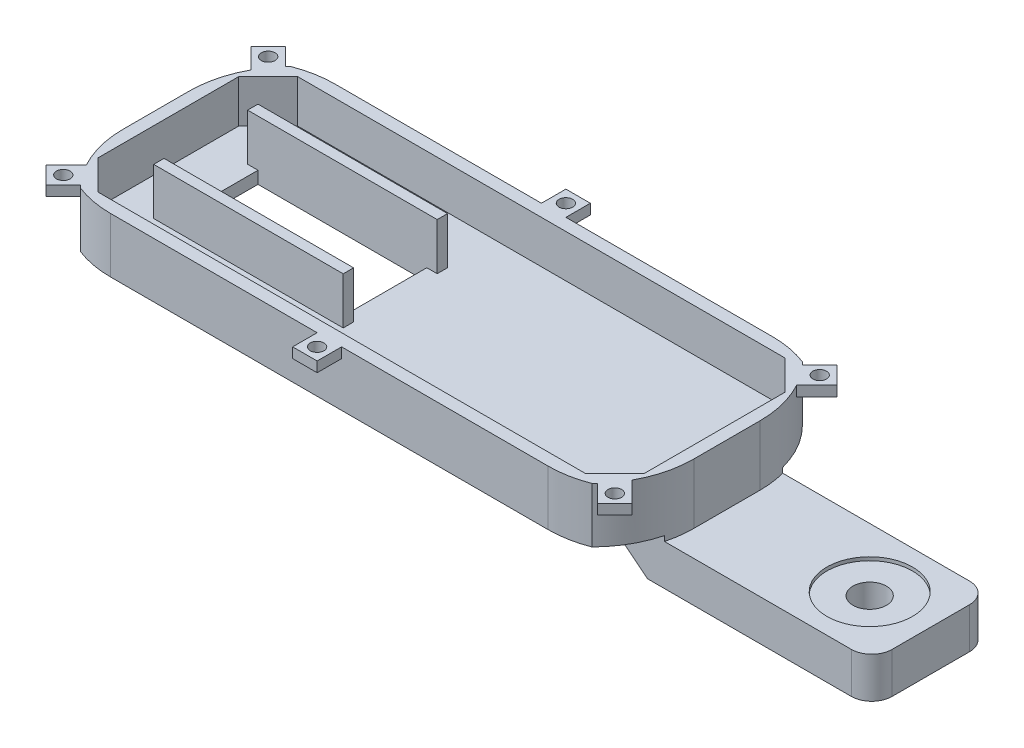
SolidWorks part; units mm, degrees
ref_plane "Front Plane" through (0, 0, 0) normal (0, 0, 1) x (1, 0, 0)
ref_plane "Top Plane" through (0, 0, 0) normal (0, 1, 0) x (1, 0, 0)
ref_plane "Right Plane" through (0, 0, 0) normal (1, 0, 0) x (0, 0, -1)
sketch "Sketch1" plane through (0, 0, 0) normal (0, 1, 0) x (1, 0, 0)
  line L0 (0, 46) -> (9, 55)
  line L1 (9, 0) -> (131, 0)
  line L2 (0, 9) -> (0, 46)
  line L3 (9, 55) -> (131, 55)
  line L4 (140, 9) -> (140, 46)
  line L5 (0, 9) -> (9, 0)
  line L6 (131, 55) -> (140, 46)
  line L7 (131, 0) -> (140, 9)
  point P0 (0, 0)
  point P1 (140, 55)
  point P2 (0, 55)
  point P3 (140, 0)
  dimension "D1" = 55
  dimension "D2" = 140
extrude "Boss-Extrude1" add sketch "Sketch1" along normal blind 30
sketch "Sketch2" plane through (0, 30, 0) normal (0, 1, 0) x (1, 0, 0)
  line L8 (3, 44.7574) -> (3, 10.2426)
  line L9 (10.2426, 3) -> (129.7574, 3)
  line L10 (137, 10.2426) -> (137, 44.7574)
  line L11 (129.7574, 52) -> (10.2426, 52)
  line L12 (3, 44.7574) -> (3, 10.2426)
  line L13 (10.2426, 3) -> (129.7574, 3)
  line L14 (137, 10.2426) -> (137, 44.7574)
  line L15 (129.7574, 52) -> (10.2426, 52)
  line L20 (3, 10.2426) -> (10.2426, 3)
  line L21 (3, 10.2426) -> (10.2426, 3)
  line L22 (129.7574, 3) -> (137, 10.2426)
  line L23 (129.7574, 3) -> (137, 10.2426)
  line L24 (137, 44.7574) -> (129.7574, 52)
  line L25 (137, 44.7574) -> (129.7574, 52)
  line L26 (10.2426, 52) -> (3, 44.7574)
  line L27 (10.2426, 52) -> (3, 44.7574)
  dimension "D1" = 3
shell "Shell2" thickness 3
extrude "Cut-Extrude2" cut sketch "Sketch2" against normal up to next
sketch "Length from bottom to Gear/Pin connection" plane through (0, 0, 0) normal (0, -1, 0) x (1, 0, 0)
  line L0 (0, -27.5) -> (25, -27.5) construction
  line L1 (0, -13.6125) -> (0, 13.6125) construction
  circle A0 centre (25, -27.5) radius 6.9102
  dimension "D1" = 25
sketch "Sketch4" plane through (0, 0, 0) normal (0, -1, 0) x (1, 0, 0)
  circle A0 centre (25, -27.5) radius 3.8
  dimension "D1" = 7.6
sketch "Outline of actual motor" plane through (0, 3, 0) normal (0, 1, 0) x (1, 0, 0)
  line L0 (15, 37.5) -> (55.9, 37.5) construction
  line L1 (55.9, 37.5) -> (55.9, 17.5) construction
  line L2 (55.9, 17.5) -> (15, 17.5) construction
  line L3 (15, 17.5) -> (15, 37.5) construction
  line L4 (55.2, 37.5) -> (15.7, 37.5) construction
  line L5 (15.7, 17.5) -> (55.2, 17.5) construction
  line L6 (55.9, 18.2) -> (55.9, 36.8) construction
  line L7 (15, 36.8) -> (15, 18.2) construction
  dimension "D1" = 0
  dimension "D2" = 0
  dimension "D3" = 0
  dimension "D4" = 0
sketch "Outline of motor press fit" plane through (0, 3, 0) normal (0, 1, 0) x (1, 0, 0)
  line L8 (15, 37.5) -> (55.9, 37.5) construction
  line L9 (14.75, 17.25) -> (56.15, 17.25)
  line L10 (14.75, 17.25) -> (14.75, 37.75)
  line L11 (14.75, 37.75) -> (56.15, 37.75)
  line L12 (56.15, 17.25) -> (56.15, 37.75)
  line L13 (55.9, 37.5) -> (55.9, 17.5) construction
  line L14 (55.9, 17.5) -> (15, 17.5) construction
  line L15 (15, 17.5) -> (15, 37.5) construction
  dimension "D1" = 0.25
  dimension "D2" = 0.25
  dimension "D3" = 0.25
  dimension "D4" = 0.25
sketch "Sketch16" plane through (0, 3, 0) normal (0, 1, 0) x (1, 0, 0)
  line L0 (18.21, 40.29) -> (52.69, 40.29)
  line L1 (52.69, 37.75) -> (18.21, 37.75)
  line L2 (18.21, 17.25) -> (52.69, 17.25)
  line L3 (52.69, 14.71) -> (18.21, 14.71)
  line L4 (14.75, 37.75) -> (12.21, 37.75)
  line L5 (12.21, 37.75) -> (58.69, 37.75)
  line L6 (58.69, 17.25) -> (56.15, 17.25)
  line L7 (12.21, 17.25) -> (14.75, 17.25)
  line L8 (12.21, 40.29) -> (18.21, 40.29) construction
  line L9 (12.21, 40.29) -> (12.21, 37.75) construction
  line L12 (12.21, 14.71) -> (58.69, 14.71)
  line L13 (58.69, 14.71) -> (58.69, 40.29)
  line L14 (58.69, 40.29) -> (12.21, 40.29)
  line L15 (12.21, 40.29) -> (12.21, 14.71)
  line L16 (12.21, 14.71) -> (18.21, 14.71)
  line L17 (58.69, 14.71) -> (58.69, 17.25)
  line L18 (58.69, 40.29) -> (52.69, 40.29)
  line L19 (12.21, 40.29) -> (12.21, 37.75)
  line L21 (14.75, 37.75) -> (56.15, 37.75) construction
  line L22 (18.21, 37.75) -> (14.75, 37.75)
  line L24 (35.45, 40.29) -> (35.45, 14.71) construction
  line L25 (12.21, 27.5) -> (58.69, 27.5) construction
  line L26 (18.21, 40.29) -> (12.21, 40.29)
  line L27 (12.21, 17.25) -> (12.21, 14.71)
  line L29 (58.69, 40.29) -> (58.69, 37.75)
  line L31 (52.69, 37.75) -> (56.15, 37.75)
  line L33 (52.69, 40.29) -> (58.69, 40.29)
  line L34 (52.69, 14.71) -> (58.69, 14.71)
  line L36 (52.69, 17.25) -> (56.15, 17.25)
  line L39 (58.69, 14.71) -> (58.69, 17.25)
  line L40 (18.21, 14.71) -> (12.21, 14.71)
  line L42 (18.21, 17.25) -> (14.75, 17.25)
  line L45 (12.21, 14.71) -> (12.21, 17.25)
  line L46 (58.69, 37.75) -> (58.69, 40.29)
  line L47 (52.69, 14.71) -> (58.69, 14.71)
  dimension "D2" = 6
  dimension "D1" = 2.54
extrude "Boss-Extrude5" add sketch "Sketch16" along normal blind 25.5 contours L29 L18 L0 L26 L19 L4 L5 L1 | L2 L42 L7 L27 L16 L3 L34 L17 L6 L36 region at (35.45, 3, -39.02) region at (35.45, 3, -15.98)
sketch "Sketch17" plane through (0, 28.5, 0) normal (0, 1, 0) x (1, 0, 0)
  line L0 (58.69, 40.29) -> (12.21, 40.29) construction
  line L1 (56.193, 40.29) -> (64.193, 40.29)
  line L2 (56.193, 40.29) -> (56.193, 14.71)
  line L3 (56.193, 14.71) -> (64.193, 14.71)
  line L4 (64.193, 40.29) -> (64.193, 14.71)
  line L5 (14.75, 37.75) -> (14.75, 40.29) construction
  line L6 (58.69, 40.29) -> (12.21, 40.29) construction
  line L8 (14.75, 40.29) -> (6.75, 40.29)
  line L9 (14.75, 40.29) -> (14.75, 14.71)
  line L10 (14.75, 14.71) -> (6.75, 14.71)
  line L11 (6.75, 40.29) -> (6.75, 14.71)
  dimension "D1" = 8
  dimension "D2" = 8
extrude "Boss-Extrude6" add sketch "Sketch17" against normal blind 5
sketch "Sketch18" plane through (0, 28.5, 0) normal (0, 1, 0) x (1, 0, 0)
  circle A0 centre (59.75, 32.5) radius 1.75
  circle A1 centre (59.75, 22.5) radius 1.75
  circle A2 centre (11.15, 22.5) radius 1.75
  circle A3 centre (11.15, 32.5) radius 1.75
  dimension "D1" = 3.5
  dimension "D2" = 3.5
  dimension "D3" = 3.5
  dimension "D4" = 3.5
extrude "Cut-Extrude3" cut sketch "Sketch18" against normal up to next
sketch "Sketch20" plane through (0, 30, 0) normal (0, 1, 0) x (1, 0, 0)
  line L1 (-8.4121, 65.847) -> (189.0699, 65.847)
  line L2 (-8.4121, 65.847) -> (-8.4121, -17.3253)
  line L3 (-8.4121, -17.3253) -> (189.0699, -17.3253)
  line L4 (189.0699, 65.847) -> (189.0699, -17.3253)
extrude "Cut-Extrude4" cut sketch "Sketch20" against normal offset from surface (16.5 mm away) 13.5 up to face at (70, 0, -27.5)
sketch "Sketch21" plane through (0, 0, 0) normal (0, 0, 1) x (1, 0, 0)
  line L0 (80.8737, 0) -> (80.8737, 13.5) construction
  line L1 (30.25, 0) -> (-30.25, 0) construction
  dimension "D1" = 13.5
extrude "Cut-Extrude5" cut sketch "Outline of motor press fit" against normal up to next
sketch "Sketch24" plane through (0, 13.5, 0) normal (0, 1, 0) x (1, 0, 0)
  line L1 (12.21, 40.29) -> (58.69, 40.29)
  line L2 (12.21, 40.29) -> (12.21, 37.75)
  line L3 (12.21, 37.75) -> (58.69, 37.75)
  line L4 (58.69, 40.29) -> (58.69, 37.75)
  line L5 (12.21, 17.25) -> (58.69, 17.25)
  line L6 (12.21, 17.25) -> (12.21, 14.71)
  line L7 (12.21, 14.71) -> (58.69, 14.71)
  line L8 (58.69, 17.25) -> (58.69, 14.71)
extrude "Boss-Extrude7" add sketch "Sketch24" along normal blind 1
sketch "Sketch25" plane through (140, 0, 0) normal (1, 0, 0) x (0, 0, -1)
  line L0 (27.5, 0) -> (27.5, -1.25) construction
  line L1 (20.5898, 0) -> (34.4102, 0) construction
  line L2 (27.5, 0) -> (27.5, -11.25) construction
  dimension "D1" = 1.25
  dimension "D2" = 11.25
sketch "Sketch26" plane through (140, 0, 0) normal (1, 0, 0) x (0, 0, -1)
  line L0 (27.5, 0) -> (42, 0) construction
  line L1 (20.5898, 0) -> (34.4102, 0) construction
  line L2 (9, 0) -> (46, 0) construction
  line L3 (27.5, 0) -> (13, 0) construction
  line L5 (13, 0) -> (42, 0)
  line L6 (13, 0) -> (13, -11.25)
  line L7 (13, -11.25) -> (42, -11.25)
  line L8 (42, 0) -> (42, -11.25)
  dimension "D1" = 14.5
  dimension "D2" = 14.5
extrude "Boss-Extrude8" add sketch "Sketch26" along normal blind 55 from offset 5 offset against normal yes
sketch "Sketch27" plane through (0, 0, -13) normal (0, 0, 1) x (1, 0, 0)
  line L0 (135, -11.25) -> (121, 0)
  line L1 (9, 0) -> (131, 0) construction
  line L2 (121, 0) -> (135, 0)
  line L3 (135, 0) -> (135, -11.25) construction
  line L4 (131, 0) -> (140, 0) construction
  line L5 (135, 0) -> (135, -11.25)
  dimension "D1" = 14
extrude "Boss-Extrude9" add sketch "Sketch27" against normal up to surface (29 mm away) up to face at (158, -4.5, -42)
sketch "Sketch31" plane through (190, 0, 0) normal (1, 0, 0) x (0, 0, -1)
  line L0 (13, 0) -> (13, -11.25) construction
  line L1 (42, 0) -> (13, 0)
  line L2 (42, 0) -> (42, -1.25)
  line L3 (42, -1.25) -> (13, -1.25)
  line L4 (13, 0) -> (13, -1.25)
  dimension "D1" = 1.25
extrude "Cut-Extrude8" cut sketch "Sketch31" against normal up to surface (50 mm away) up to face at (140, 4.5, -27.5)
sketch "Sketch32" plane through (0, -1.25, 0) normal (0, 1, 0) x (1, 0, 0)
  line L0 (140, 27.5) -> (175, 27.5) construction
  line L1 (140, 46) -> (140, 9) construction
  circle A0 centre (175, 27.5) radius 10.5
  dimension "D2" = 21
  dimension "D1" = 35
extrude "Cut-Extrude9" cut sketch "Sketch32" against normal blind 0.85
sketch "Sketch33" plane through (0, -2.1, 0) normal (0, 1, 0) x (1, 0, 0)
  circle A0 centre (175, 27.5) radius 4.1
  dimension "D1" = 8.2
extrude "Cut-Extrude10" cut sketch "Sketch33" against normal blind 7.25
sketch "Sketch35" plane through (0, 13.5, 0) normal (0, 1, 0) x (1, 0, 0)
  line L0 (0, 27.5) -> (53, 27.5) construction
  line L1 (9, 55) -> (0, 46) construction
  line L2 (9, 55) -> (131, 55) construction
  line L3 (73, 55) -> (67, 55)
  line L4 (0, -14.1625) -> (0, 14.1625) construction
  line L5 (0, 46) -> (9, 55) construction
  line L6 (6.6213, 52.6213) -> (2.3787, 48.3787)
  line L7 (2.3787, 48.3787) -> (-1.864, 52.6213)
  line L8 (-1.864, 52.6213) -> (2.3787, 56.864)
  line L9 (2.3787, 56.864) -> (6.6213, 52.6213)
  line L10 (131, 55) -> (140, 46) construction
  line L11 (137.6213, 48.3787) -> (133.3787, 52.6213)
  line L12 (133.3787, 52.6213) -> (137.6213, 56.864)
  line L13 (137.6213, 56.864) -> (141.864, 52.6213)
  line L14 (141.864, 52.6213) -> (137.6213, 48.3787)
  line L15 (67, 55) -> (67, 61)
  line L16 (67, 61) -> (73, 61)
  line L17 (73, 61) -> (73, 55)
  line L18 (137.6213, -1.864) -> (141.864, 2.3787)
  line L19 (133.3787, 2.3787) -> (137.6213, -1.864)
  line L20 (137.6213, 6.6213) -> (133.3787, 2.3787)
  line L21 (141.864, 2.3787) -> (137.6213, 6.6213)
  line L22 (67, -6) -> (73, -6)
  line L23 (67, 0) -> (67, -6)
  line L24 (73, 0) -> (67, 0)
  line L25 (73, -6) -> (73, 0)
  line L26 (-1.864, 2.3787) -> (2.3787, -1.864)
  line L27 (2.3787, 6.6213) -> (-1.864, 2.3787)
  line L28 (6.6213, 2.3787) -> (2.3787, 6.6213)
  line L29 (2.3787, -1.864) -> (6.6213, 2.3787)
  point P13 (4.5, 50.5)
  point P22 (135.5, 50.5)
  point P27 (70, 55)
  dimension "D1" = 6
  dimension "D2" = 6
  dimension "D3" = 6
  dimension "D4" = 6
  dimension "D5" = 6
  dimension "D6" = 6
extrude "Boss-Extrude11" add sketch "Sketch35" against normal blind 2.5
sketch "Sketch44" plane through (0, 13.5, 0) normal (0, 1, 0) x (1, 0, 0)
  line L0 (2.3787, 56.864) -> (2.3787, 48.3787) construction
  line L1 (67, 61) -> (73, 55) construction
  line L2 (137.6213, 56.864) -> (137.6213, 48.3787) construction
  line L3 (137.6213, 6.6213) -> (137.6213, -1.864) construction
  line L4 (67, 0) -> (73, -6) construction
  line L5 (2.3787, 6.6213) -> (2.3787, -1.864) construction
  line L6 (0, 27.5) -> (53, 27.5) construction
  circle A0 centre (2.3787, 2.3787) radius 1.675
  circle A1 centre (70, -3) radius 1.675
  circle A2 centre (137.6213, 2.3787) radius 1.675
  circle A3 centre (137.6213, 52.6213) radius 1.675
  circle A4 centre (70, 58) radius 1.675
  circle A5 centre (2.3787, 52.6213) radius 1.675
  dimension "D1" = 3.35
  dimension "D2" = 3.35
  dimension "D3" = 3.35
extrude "Cut-Extrude11" cut sketch "Sketch44" against normal up to surface (2.5 mm away) contours A5 | A4 | A3 | A2 | A1 | A0 | A5 region at (2.3787, 13.5, -2.3787) region at (70, 13.5, 3) region at (137.6213, 13.5, -2.3787) region at (137.6213, 13.5, -52.6213) region at (70, 13.5, -58) region at (2.3787, 13.5, -52.6213) up to face at (70, 11, -58)
fillet "Fillet1" radius 25 4 edges at (0, 6.75, -46) (0, 6.75, -9) (140, 6.75, -46) (140, 6.75, -9)
fillet "Fillet2" radius 25 4 edges at (131, 6.75, -55) (131, 6.75, 0) (9, 6.75, 0) (9, 6.75, -55)
fillet "Fillet3" radius 5 2 edges at (190, -6.25, -42) (190, -6.25, -13)
equation "\"arm width\"=55"
equation "\"D1@Sketch1\"=\"arm width\""
equation "\"arm length\"=140"
equation "\"D2@Sketch1\"=\"arm length\""
equation "\"screwHoleDiameterMG996R\"= 3.5"
equation "\"D1@Sketch18\"=\"screwHoleDiameterMG996R\""
equation "\"D2@Sketch18\"=\"screwHoleDiameterMG996R\""
equation "\"D3@Sketch18\"=\"screwHoleDiameterMG996R\""
